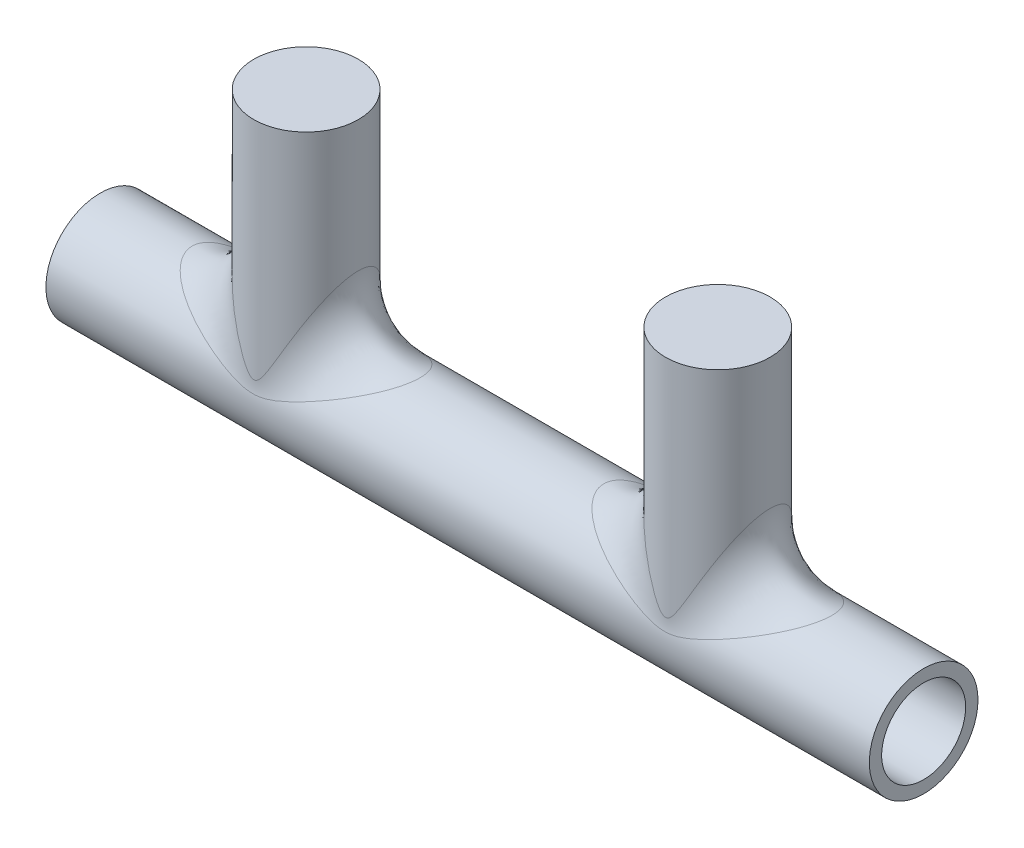
SolidWorks part; units mm, degrees
ref_plane "Front Plane" through (0, 0, 0) normal (0, 0, 1) x (1, 0, 0)
ref_plane "Top Plane" through (0, 0, 0) normal (0, 1, 0) x (1, 0, 0)
ref_plane "Right Plane" through (0, 0, 0) normal (1, 0, 0) x (0, 0, -1)
sketch "Sketch1" plane through (0, 0, 0) normal (1, 0, 0) x (0, 0, -1)
  circle A0 centre (0, 0) radius 5.1
  circle A1 centre (0, 0) radius 6.6
  dimension "D1" = 10.2
  dimension "D2" = 1.5
extrude "Boss-Extrude1" add sketch "Sketch1" along normal blind 100
sketch "Sketch3" plane through (0, 0, 0) normal (0, 1, 0) x (1, 0, 0)
  line L0 (0, 6.6) -> (0, -6.6) construction
  line L2 (100, -6.6) -> (100, 6.6) construction
  circle A0 centre (25, 0) radius 6.35
  circle A1 centre (75, 0) radius 6.35
  point P8 (100, 0.8364)
  dimension "D3" = 12.7
  dimension "D4" = 12.7
  dimension "D1" = 25
  dimension "D2" = 25
extrude "Boss-Extrude2" add sketch "Sketch3" along normal blind 30
extrude "Cut-Extrude1" cut sketch "Sketch1<2>" along normal through all contours A0 region at (0, 0, 0)
sketch "Sketch1<2>" plane through (0, 0, 0) normal (1, 0, 0) x (0, 0, -1) same geometry as "Sketch1"
fillet "Fillet1" radius 7.5 2 edges at (74.8769, 1.8035, 6.3488) (24.8769, 1.8035, 6.3488)
